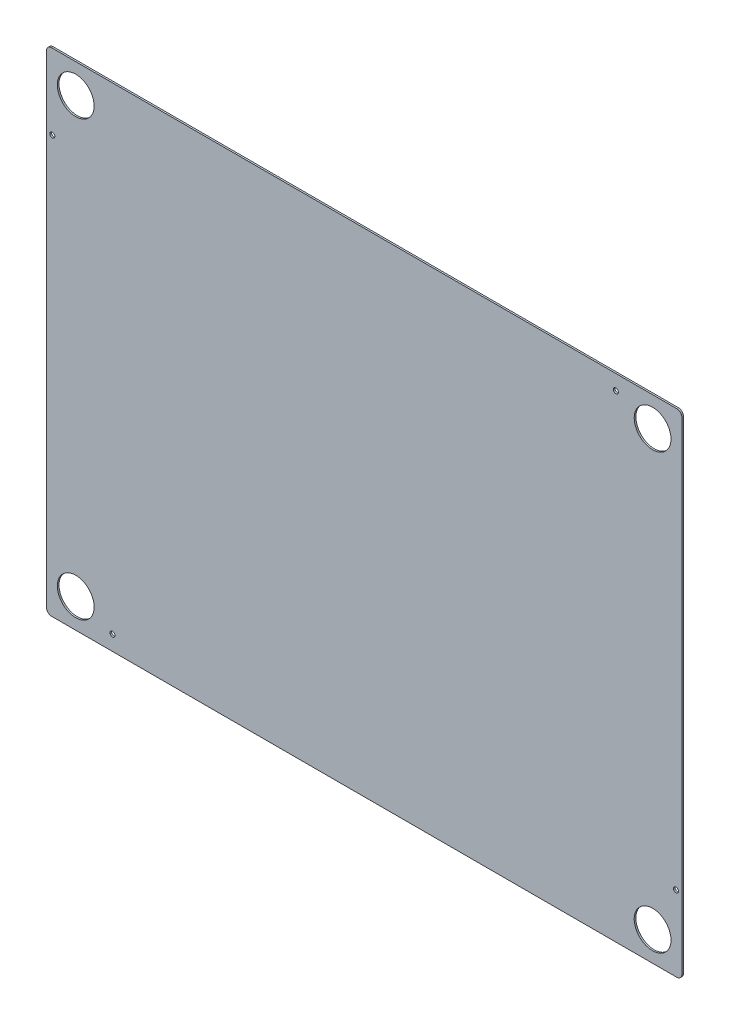
SolidWorks part; units mm, degrees
ref_plane "Front Plane" through (0, 0, 0) normal (0, 0, 1) x (1, 0, 0)
ref_plane "Top Plane" through (0, 0, 0) normal (0, 1, 0) x (1, 0, 0)
ref_plane "Right Plane" through (0, 0, 0) normal (1, 0, 0) x (0, 0, -1)
sketch "Sketch1" plane through (0, 0, 0) normal (0, 0, 1) x (1, 0, 0)
  line L0 (0, 147.25) -> (0, -147.25) construction
  line L1 (190, -147.25) -> (-190, -147.25)
  line L2 (190, -147.25) -> (190, 147.25)
  line L3 (190, 147.25) -> (-190, 147.25)
  line L4 (-190, -147.25) -> (-190, 147.25)
  line L5 (190, -147.25) -> (-190, 147.25) construction
  line L6 (190, 147.25) -> (-190, -147.25) construction
  line L7 (0.55, 0) -> (-0.55, 0) construction
  circle A2 centre (-172.5, 129.75) radius 11
  circle A3 centre (172.5, 129.75) radius 11
  circle A4 centre (172.5, -129.75) radius 11
  circle A5 centre (-172.5, -129.75) radius 11
  circle A6 centre (150.5, 138.25) radius 1.5
  circle A8 centre (-186.5, 102.25) radius 1.5
  circle A9 centre (-150.5, -138.25) radius 1.5
  circle A10 centre (186.5, -102.25) radius 1.5
  point P0 (0, 0)
  dimension "D3" = 17.5
  dimension "D1" = 294.5
  dimension "D2" = 380
  dimension "D4" = 17.5
extrude "Boss-Extrude1" add sketch "Sketch1" along normal blind 1
fillet "Fillet1" radius 3 4 edges at (190, -147.25, 0.5) (-190, -147.25, 0.5) (-190, 147.25, 0.5) (190, 147.25, 0.5)
